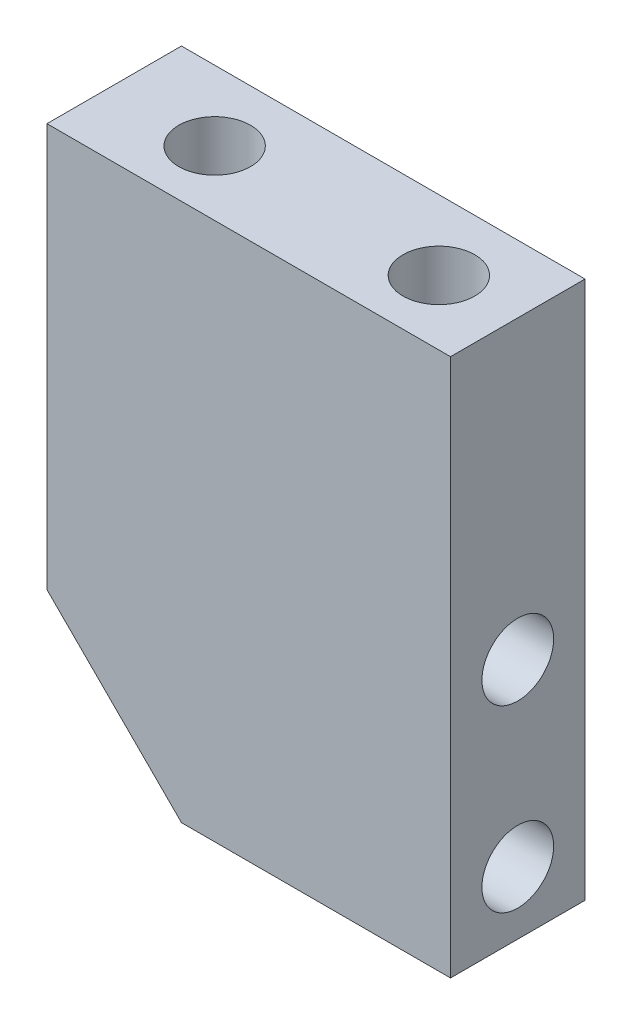
SolidWorks part; units mm, degrees
ref_plane "Płaszczyzna przednia" through (0, 0, 0) normal (0, 0, 1) x (1, 0, 0)
ref_plane "Płaszczyzna górna" through (0, 0, 0) normal (0, 1, 0) x (1, 0, 0)
ref_plane "Płaszczyzna prawa" through (0, 0, 0) normal (1, 0, 0) x (0, 0, -1)
sketch "Szkic1" plane through (0, 0, 0) normal (0, 0, 1) x (1, 0, 0)
  line L1 (22.5, -30) -> (-22.5, -30)
  line L2 (22.5, -30) -> (22.5, 30)
  line L3 (22.5, 30) -> (-22.5, 30)
  line L4 (-22.5, -30) -> (-22.5, 30)
  line L5 (22.5, -30) -> (-22.5, 30) construction
  line L6 (22.5, 30) -> (-22.5, -30) construction
  point P0 (0, 0)
  dimension "D1" = 45
  dimension "D2" = 60
extrude "Dodanie-wyciągnięcie1" add sketch "Szkic1" along normal blind 15
sketch "Szkic3" plane through (0, 30, 0) normal (0, 1, 0) x (1, 0, 0)
  line L0 (22.5, -15) -> (22.5, 0) construction
  line L2 (22.5, 0) -> (-22.5, 0) construction
  circle A0 centre (14, -7.8) radius 4
  circle A1 centre (-11, -7.8) radius 4
  dimension "D1" = 8
  dimension "D4" = 8
  dimension "D2" = 8.5
  dimension "D3" = 7.8
  dimension "D5" = 7.8
  dimension "D6" = 25
extrude "Wytnij-wyciągnięcie1" cut sketch "Szkic3" against normal blind 15
chamfer "Sfazowanie1" distance 15 angle 45 1 edges at (-22.5, -30, 7.5)
sketch "Szkic4" plane through (22.5, 0, 0) normal (1, 0, 0) x (0, 0, -1)
  line L0 (-15, -30) -> (0, -30) construction
  line L1 (-15, -30) -> (-15, 30) construction
  circle A0 centre (-7.5, -23) radius 4
  circle A1 centre (-7.5, -3) radius 4
  dimension "D1" = 8
  dimension "D2" = 8
  dimension "D3" = 7
  dimension "D4" = 7.5
  dimension "D5" = 20
extrude "Wytnij-wyciągnięcie2" cut sketch "Szkic4" against normal blind 25
